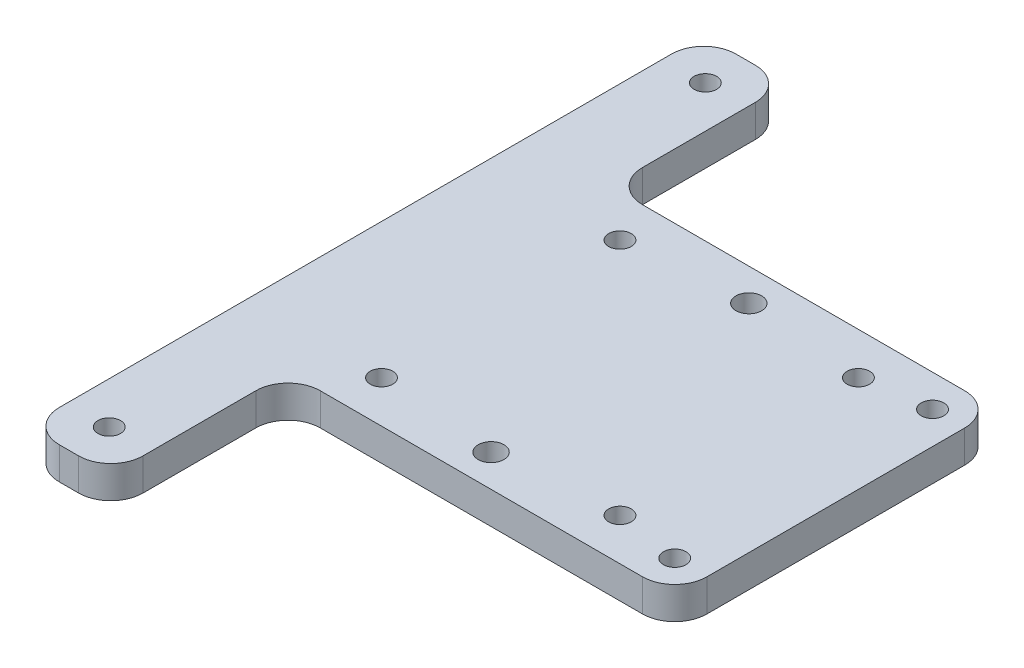
SolidWorks part; units mm, degrees
ref_plane "정면" through (0, 0, 0) normal (0, 0, 1) x (1, 0, 0)
ref_plane "윗면" through (0, 0, 0) normal (0, 1, 0) x (1, 0, 0)
ref_plane "우측면" through (0, 0, 0) normal (1, 0, 0) x (0, 0, -1)
sketch "스케치2" plane through (0, 0, 0) normal (0, 1, 0) x (1, 0, 0)
  line L0 (-60, -25) -> (-60, -52.5)
  line L1 (-60, 25) -> (0, 25)
  line L3 (-60, -25) -> (0, -25)
  line L4 (0, 25) -> (0, -25)
  line L5 (-60, 25) -> (0, -25) construction
  line L6 (-60, -25) -> (0, 25) construction
  line L11 (-73, 52.5) -> (-60, 52.5)
  line L12 (-73, 52.5) -> (-73, -52.5)
  line L13 (-73, -52.5) -> (-60, -52.5)
  line L14 (-60, 52.5) -> (-60, 25)
  line L16 (-73, 0) -> (0, 0) construction
  line L17 (-66.5, 52.5) -> (-66.5, -52.5) construction
  point P0 (-30, 0)
  point P5 (0, 0)
  point P11 (-73, 0)
  dimension "D1" = 50
  dimension "D2" = 60
  dimension "D3" = 105
  dimension "D4" = 13
extrude "보스-돌출1" add sketch "스케치2" along normal blind 5
fillet "필렛1" radius 5 8 edges at (-60, 2.5, -25) (0, 2.5, -25) (0, 2.5, 25) (-60, 2.5, 25) (-60, 2.5, 52.5) (-73, 2.5, 52.5) (-60, 2.5, -52.5) (-73, 2.5, -52.5)
sketch "스케치5" plane through (0, 5, 0) normal (0, 1, 0) x (1, 0, 0)
  circle A0 centre (-5, 20) radius 1.75
  circle A1 centre (-5, -20) radius 1.75
  dimension "D1" = 3.5
  dimension "D2" = 3.5
sketch "스케치7" plane through (0, 0, 0) normal (0, -1, 0) x (1, 0, 0)
  circle A0 centre (-66.5, -46.25) radius 1.75 construction
  circle A1 centre (-66.5, 46.25) radius 1.75 construction
  circle A2 centre (-66.5, -46.25) radius 1.75
  circle A3 centre (-66.5, 46.25) radius 1.75
extrude "컷-돌출5" cut sketch "스케치7" against normal through all
sketch "스케치8" plane through (0, 5, 0) normal (0, 1, 0) x (1, 0, 0)
  circle A0 centre (-5, 20) radius 1.75
  circle A1 centre (-5, -20) radius 1.75
  dimension "D1" = 3.5
  dimension "D2" = 3.5
extrude "컷-돌출6" cut sketch "스케치8" against normal through all
sketch "스케치9" plane through (0, 5, 0) normal (0, 1, 0) x (1, 0, 0)
  line L0 (-5, 25) -> (-55, 25) construction
  line L1 (-15, 18.5) -> (-52, 18.5) construction
  line L2 (-15, 18.5) -> (-15, -18.5) construction
  line L3 (-15, -18.5) -> (-52, -18.5) construction
  line L4 (-52, 18.5) -> (-52, -18.5) construction
  line L5 (-15, 18.5) -> (-52, -18.5) construction
  line L6 (-15, -18.5) -> (-52, 18.5) construction
  line L7 (-33.5, 25) -> (-33.5, -25) construction
  line L8 (-55, -25) -> (-5, -25) construction
  line L9 (0, -20) -> (0, 20) construction
  line L10 (-52, 0) -> (-15, 0) construction
  circle A0 centre (-52, 18.5) radius 1.75
  circle A1 centre (-52, -18.5) radius 1.75
  circle A2 centre (-15, -18.5) radius 1.75
  circle A3 centre (-15, 18.5) radius 1.75
  circle A4 centre (-33.5, 20) radius 2
  circle A5 centre (-33.5, -20) radius 2
  point P0 (-33.5, 0)
  dimension "D3" = 3.5
  dimension "D4" = 4
  dimension "D1" = 37
  dimension "D2" = 15
  dimension "D5" = 40
extrude "컷-돌출7" cut sketch "스케치9" against normal through all
ref_plane "평면1" through (-33.5, 0, 0) normal (1, 0, 0) x (0, 0, -1)
